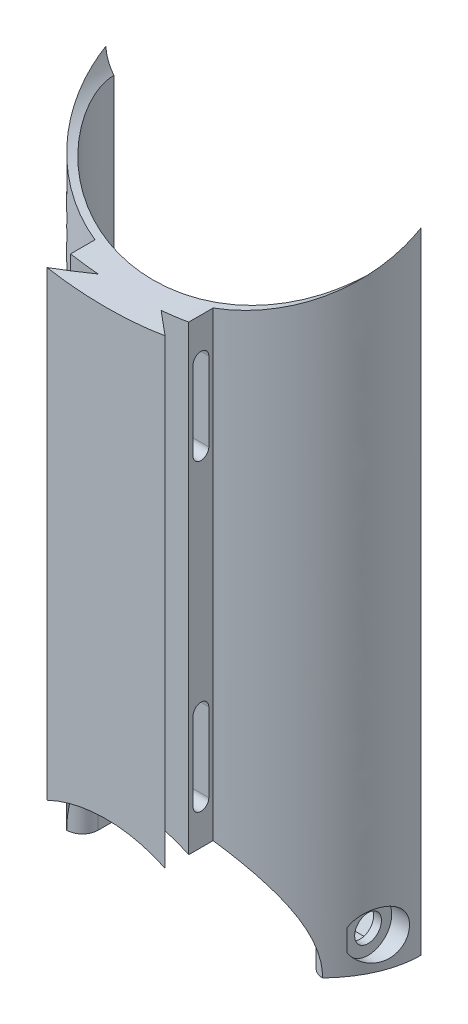
SolidWorks part; units mm, degrees
material "PLA"
ref_plane "Front Plane" through (0, 0, 0) normal (0, 0, 1) x (1, 0, 0)
ref_plane "Top Plane" through (0, 0, 0) normal (0, 1, 0) x (1, 0, 0)
ref_plane "Right Plane" through (0, 0, 0) normal (1, 0, 0) x (0, 0, -1)
sketch "Sketch1" plane through (0, 0, 0) normal (0, 1, 0) x (1, 0, 0)
  ellipse E0 centre (0, 0) end of major axis (25.4, 0) minor radius 19.05
  dimension "D1" = 50.8
  dimension "D2" = 38.1
extrude "Boss-Extrude1" add sketch "Sketch1" along normal blind 101.6 contours E0
shell "Shell1" thickness 1.27 removed face at (25.4, 101.6, 0) removed face at (25.4, 0, 0)
sketch "Sketch3" plane through (0, 0, 0) normal (0, 0, 1) x (1, 0, 0)
  line L1 (29.1836, -15.0653) -> (-40.8926, -15.0653)
  line L2 (29.1836, -15.0653) -> (29.1836, 142.3871)
  line L3 (29.1836, 142.3871) -> (-40.8926, 142.3871)
  line L4 (-40.8926, -15.0653) -> (-40.8926, 142.3871)
extrude "Cut-Extrude1" cut sketch "Sketch3" against normal up to surface up to face at (25.4, 101.6, 0)
ref_plane "Plane4" through (0, 0, 19.05) normal (0, 0, 1) x (1, 0, 0)
sketch "Sketch4" plane through (0, 0, 19.05) normal (0, 0, 1) x (1, 0, 0)
  line L1 (9.525, 101.6) -> (-9.525, 101.6)
  line L2 (9.525, 101.6) -> (9.525, 0)
  line L3 (9.525, 0) -> (-9.525, 0)
  line L4 (-9.525, 101.6) -> (-9.525, 0)
  line L6 (25.4, 101.6) -> (25.4, 0) construction
  line L7 (-25.4, 0) -> (25.4, 0) construction
  line L8 (25.4, 101.6) -> (-25.4, 101.6) construction
  dimension "D1" = 19.05
  dimension "D4" = 15.875
extrude "Boss-Extrude2" add sketch "Sketch4" against normal up to surface (1.3902 mm away) up to face at (0, 50.8, 9.525)
sketch "Sketch6" plane through (0, 0, 19.05) normal (0, 0, 1) x (1, 0, 0)
  line L4 (-9.525, 0) -> (9.525, 0)
  line L5 (9.525, 0) -> (9.525, 101.6)
  line L6 (9.525, 101.6) -> (-9.525, 101.6)
  line L7 (-9.525, 101.6) -> (-9.525, 0)
  line L8 (-9.525, 0) -> (9.525, 0)
  line L9 (9.525, 0) -> (9.525, 101.6)
  line L10 (9.525, 101.6) -> (-9.525, 101.6)
  line L11 (-9.525, 101.6) -> (-9.525, 0)
  dimension "D1" = 0
extrude "Boss-Extrude4" add sketch "Sketch6" along normal blind 6.35
sketch "Sketch7" plane through (0, 0, 0) normal (0, -1, 0) x (1, 0, 0)
  line L0 (-9.525, 25.4) -> (-5.08, 21.59)
  line L1 (9.525, 25.4) -> (5.08, 21.59)
  line L2 (-5.08, 21.59) -> (-9.525, 21.59)
  line L3 (-9.525, 17.6598) -> (-9.525, 25.4) construction
  line L4 (-9.525, 21.59) -> (-9.525, 25.4)
  line L5 (5.08, 21.59) -> (9.525, 21.59)
  line L6 (9.525, 17.6598) -> (9.525, 25.4) construction
  line L7 (9.525, 21.59) -> (9.525, 25.4)
  line L8 (-9.525, 25.4) -> (9.525, 25.4) construction
  dimension "D2" = 3.81
  dimension "D3" = 10.16
extrude "Cut-Extrude2" cut sketch "Sketch7" against normal through all
sketch "Sketch8" plane through (0, 0, 19.05) normal (0, 0, 1) x (1, 0, 0)
  line L0 (25.4, 101.6) -> (25.4, 0) construction
  line L1 (-25.4, 0) -> (-25.4, 101.6) construction
  line L3 (9.525, 101.6) -> (-9.525, 101.6) construction
  ellipse E0 centre (0, 0) end of major axis (-20.6375, 0) minor radius 19.05
  ellipse E1 centre (0, 101.6) end of major axis (25.4, 101.6) minor radius 11.1125
  dimension "D1" = 38.1
  dimension "D2" = 41.275
  dimension "D3" = 22.225
extrude "Cut-Extrude3" cut sketch "Sketch8" against normal through all both and the other way through all
sketch "Sketch10" plane through (9.525, 0, 0) normal (1, 0, 0) x (0, 0, -1)
  line L0 (-19.6215, 23.2496) -> (-19.6215, 35.9496) construction
  line L2 (-20.8915, 23.2496) -> (-20.8915, 35.9496)
  line L3 (-18.3515, 23.2496) -> (-18.3515, 35.9496)
  line L4 (-17.6598, 16.8996) -> (-21.59, 16.8996) construction
  line L6 (-21.59, 91.2984) -> (-21.59, 16.8996) construction
  line L7 (-19.6215, 72.2484) -> (-19.6215, 84.9484) construction
  line L8 (-20.8915, 72.2484) -> (-20.8915, 84.9484)
  line L9 (-18.3515, 72.2484) -> (-18.3515, 84.9484)
  line L10 (-21.59, 91.2984) -> (-17.6598, 91.2984) construction
  arc A0 (-20.8915, 23.2496) -> (-18.3515, 23.2496) centre (-19.6215, 23.2496) ccw
  arc A1 (-18.3515, 35.9496) -> (-20.8915, 35.9496) centre (-19.6215, 35.9496) ccw
  arc A2 (-20.8915, 72.2484) -> (-18.3515, 72.2484) centre (-19.6215, 72.2484) ccw
  arc A3 (-18.3515, 84.9484) -> (-20.8915, 84.9484) centre (-19.6215, 84.9484) ccw
  point P4 (-19.6215, 29.5996)
  point P13 (-19.6215, 78.5984)
  dimension "D3" = 1.27
  dimension "D6" = 1.27
  dimension "D1" = 12.7
  dimension "D2" = 12.7
  dimension "D4" = 1.9685
  dimension "D5" = 12.7
  dimension "D7" = 12.7
extrude "Cut-Extrude4" cut sketch "Sketch10" against normal through all
ref_plane "Plane7" through (20.6375, 0, 0) normal (1, 0, 0) x (0, 0, -1)
ref_plane "Plane8" through (18.0975, 0, 0) normal (1, 0, 0) x (0, 0, -1)
sketch "Sketch14" plane through (18.0975, 0, 0) normal (1, 0, 0) x (0, 0, -1)
  line L1 (-11.1054, 0) -> (0, 0)
  line L2 (-11.1054, 0) -> (-11.1054, 10.16)
  line L3 (-11.1054, 10.16) -> (0, 10.16)
  line L4 (0, 0) -> (0, 10.16)
  dimension "D1" = 10.16
extrude "Boss-Extrude7" add sketch "Sketch14" along normal up to body separate body
sketch "Sketch15" plane through (18.0975, 0, 0) normal (-1, 0, 0) x (0, 0, 1)
  line L2 (11.1054, 10.16) -> (11.1054, 0) construction
  line L3 (11.1054, 0) -> (0, 0) construction
  circle A0 centre (5.5555, 5.08) radius 2.159
  dimension "D1" = 4.318
  dimension "D2" = 5.5499
  dimension "D3" = 5.08
extrude "Cut-Extrude7" cut sketch "Sketch15" against normal through all
sketch "Sketch16" plane through (18.0975, 0, 0) normal (-1, 0, 0) x (0, 0, 1)
  line L0 (0, 10.16) -> (11.1054, 10.16) construction
  line L1 (7.5719, 1.5875) -> (9.5883, 5.08)
  line L2 (9.5883, 5.08) -> (7.5719, 8.5725)
  line L3 (7.5719, 8.5725) -> (3.5391, 8.5725)
  line L4 (3.5391, 8.5725) -> (1.5227, 5.08)
  line L5 (1.5227, 5.08) -> (3.5391, 1.5875)
  line L6 (3.5391, 1.5875) -> (7.5719, 1.5875)
  circle A0 centre (5.5555, 5.08) radius 3.4925 construction
  dimension "D1" = 6.985
extrude "Cut-Extrude8" cut sketch "Sketch16" against normal blind 3.048
mirror "Mirror5" about plane through (0, 0, 0) normal (1, 0, 0) of "Cut-Extrude7", "Boss-Extrude7", "Cut-Extrude8"
fillet "Fillet2" radius 2.54 2 edges at (18.0975, 5.08, 11.1054) (-18.0975, 5.08, 11.1054)
sketch "Sketch17" plane through (-21.1455, 0, 0) normal (1, 0, 0) x (0, 0, -1)
  circle A0 centre (-5.5555, 5.08) radius 3.81
  dimension "D1" = 7.62
extrude "Cut-Extrude9" cut sketch "Sketch17" against normal up to surface (2.8776 mm away) from offset 1.27 up to face at (-19.3757, 41.8423, 9.7714) offset against normal yes
mirror "Mirror7" about plane through (0, 0, 0) normal (1, 0, 0) of "Cut-Extrude9"
